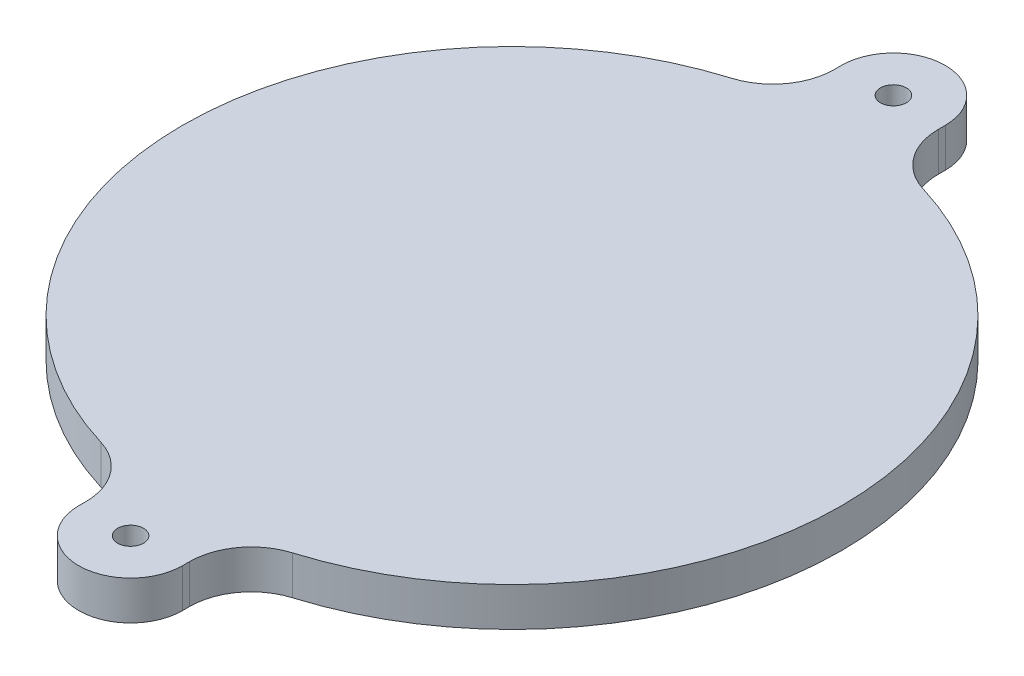
SolidWorks part; units mm, degrees
material "Acrylic (Medium-high impact)"
ref_plane "Front Plane" through (0, 0, 0) normal (0, 0, 1) x (1, 0, 0)
ref_plane "Top Plane" through (0, 0, 0) normal (0, 1, 0) x (1, 0, 0)
ref_plane "Right Plane" through (0, 0, 0) normal (1, 0, 0) x (0, 0, -1)
sketch "Sketch1" plane through (0, -0.3969, 0) normal (0, -1, 0) x (1, 0, 0)
  line L0 (0, 29.4) -> (0, -29.4) construction
  line L1 (4, 29.4) -> (4, -29.4)
  line L2 (-4, 29.4) -> (-4, -29.4)
  circle A0 centre (0, 0) radius 25.4
  circle A1 centre (0, 0) radius 25.4 construction
  arc A2 (4, 29.4) -> (-4, 29.4) centre (0, 29.4) ccw
  arc A3 (-4, -29.4) -> (4, -29.4) centre (0, -29.4) ccw
  circle A4 centre (0, 29.4) radius 1
  circle A5 centre (0, -29.4) radius 1
  point P7 (0, 0)
  circle M3 centre (0, 0) radius 25.4
  circle M4 centre (-22.225, 0) radius 1
  circle M5 centre (22.225, 0) radius 1
  dimension "D1" = 2
  dimension "D2" = 8
extrude "Boss-Extrude1" add sketch "Sketch1" along normal blind 3 contours L2 M3 M4 | L0 A0 L2 M3 | L0 A0 L1 M3 | L1 M3 M5 | A4 L1 A2 L2 A0 M3 | L2 A3 L1 A0 A5 M3 | M4 | M5 region at (-2.0154, -0.3969, 25.4357) region at (1.9958, -0.3969, 0) region at (-1.9958, -0.3969, 0) region at (2.0154, -0.3969, -25.4357) region at (12.9358, -0.3969, 0) region at (-12.9358, -0.3969, 0) region at (-22.225, -0.3969, 0) region at (22.225, -0.3969, 0)
fillet "Fillet1" radius 4.7625 4 edges at (-4, -1.8969, -25.0831) (4, -1.8969, -25.0831) (4, -1.8969, 25.0831) (-4, -1.8969, 25.0831)
